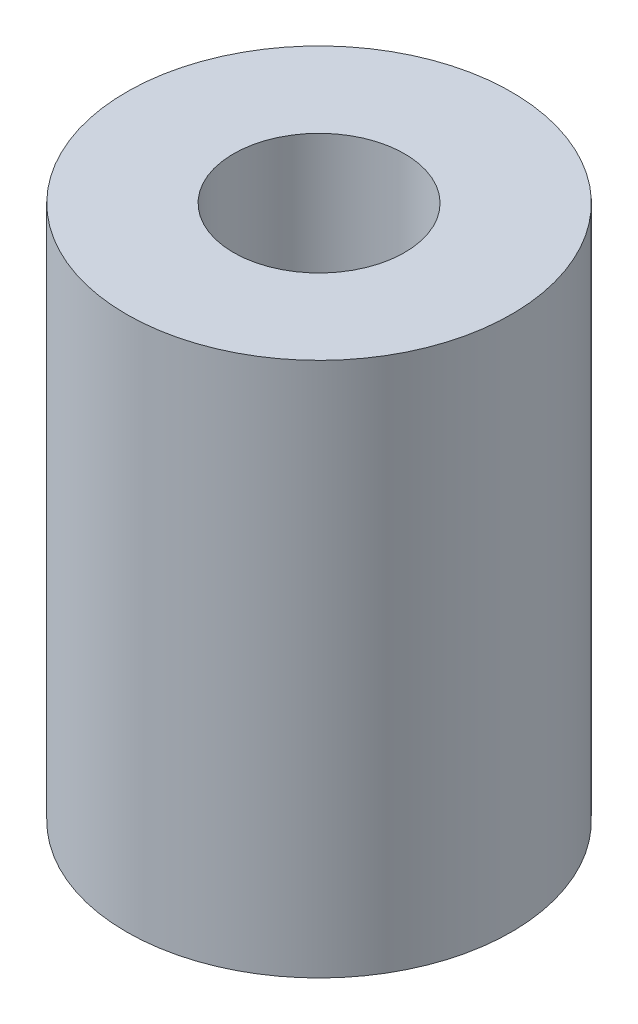
SolidWorks part; units mm, degrees
material "6061-T4 (SS)"
ref_plane "Front Plane" through (0, 0, 0) normal (0, 0, 1) x (1, 0, 0)
ref_plane "Top Plane" through (0, 0, 0) normal (0, 1, 0) x (1, 0, 0)
ref_plane "Right Plane" through (0, 0, 0) normal (1, 0, 0) x (0, 0, -1)
sketch "Sketch1" plane through (0, 0, 0) normal (0, 1, 0) x (1, 0, 0)
  line L0 (1.6, 0) -> (3.6, 0) construction
  circle A0 centre (0, 0) radius 1.6
  circle A1 centre (0, 0) radius 3.6
  dimension "D1" = 3.2
  dimension "D2" = 2
extrude "Boss-Extrude1" add sketch "Sketch1" along normal blind 10
